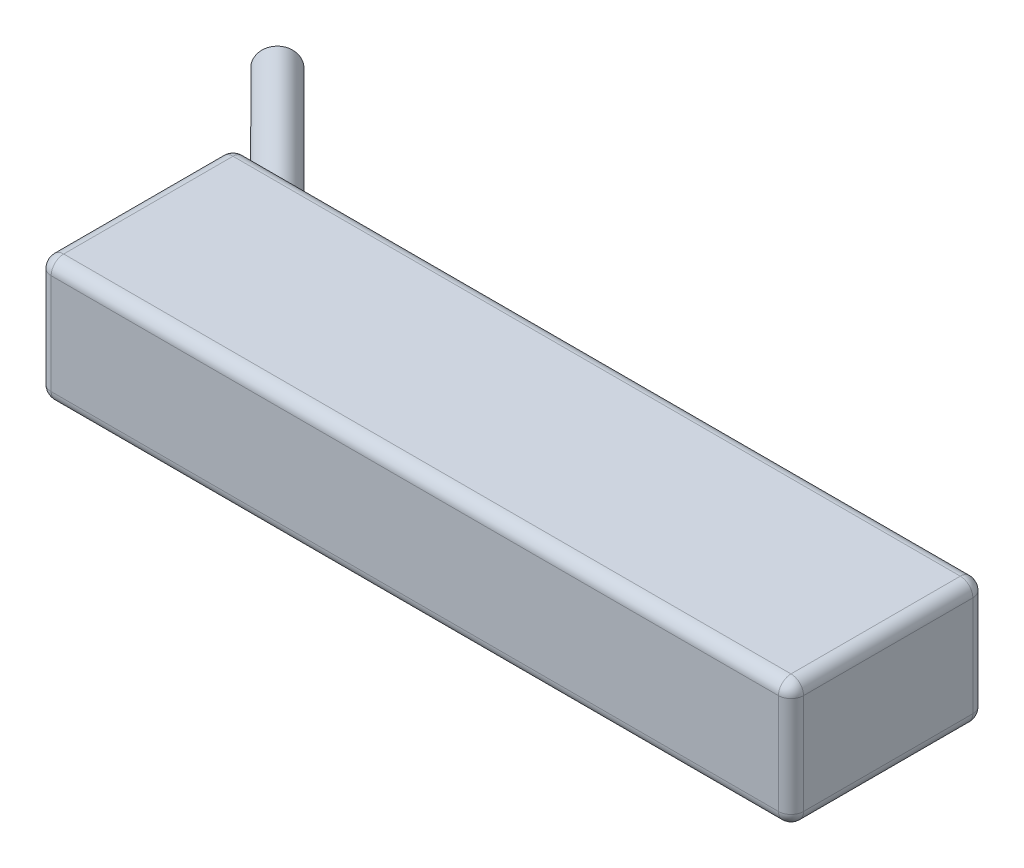
SolidWorks part; units mm, degrees
ref_plane "Front Plane" through (0, 0, 0) normal (0, 0, 1) x (1, 0, 0)
ref_plane "Top Plane" through (0, 0, 0) normal (0, 1, 0) x (1, 0, 0)
ref_plane "Right Plane" through (0, 0, 0) normal (1, 0, 0) x (0, 0, -1)
ref_axis "X" through (-88.99, 0, 0) along (1, 0, 0)
ref_axis "Y" through (0, 55, 0) along (0, -1, 0)
ref_axis "Z" through (0, 0, -88.99) along (0, 0, 1)
sketch "Sketch1" plane through (0, 0, 0) normal (0, 1, 0) x (1, 0, 0)
  line L1 (-60, 15.5) -> (60, 15.5)
  line L2 (-60, 15.5) -> (-60, -15.5)
  line L3 (-60, -15.5) -> (60, -15.5)
  line L4 (60, 15.5) -> (60, -15.5)
  line L5 (-60, 15.5) -> (60, -15.5) construction
  line L6 (-60, -15.5) -> (60, 15.5) construction
  point P0 (0, 0)
  dimension "D1" = 31
  dimension "D2" = 120
extrude "Boss-Extrude1" add sketch "Sketch1" along normal mid plane 20
sketch "Sketch3" plane through (0, 0, 0) normal (0, 1, 0) x (1, 0, 0)
  line L0 (-60, 15.5) -> (-60, 5.5)
  line L1 (-60, 5.5) -> (-50, 15.5)
  line L2 (-50, 15.5) -> (-60, 15.5)
  line L3 (-60, 15.5) -> (-55, 10.5) construction
  dimension "D1" = 45
  dimension "D2" = 10
ref_plane "Plane1" through (-32.75, 0, -32.75) normal (0.7071, 0, 0.7071) x (0.7071, 0, -0.7071)
sketch "Sketch4" plane through (-32.75, 0, -32.75) normal (0.7071, 0, 0.7071) x (0.7071, 0, -0.7071)
  line L0 (-26.4663, 4) -> (-26.4663, -4) construction
  line L1 (0, 0) -> (-26.4663, 0) construction
  line L2 (-31.4663, 10) -> (-31.4663, -10) construction
  circle A0 centre (-26.4663, 4) radius 3
  circle A1 centre (-26.4663, -4) radius 3
  dimension "D1" = 6
  dimension "D2" = 6
  dimension "D3" = 8
  dimension "D4" = 5
extrude "Boss-Extrude2" add sketch "Sketch4" against normal blind 30
fillet "Fillet1" radius 2 12 edges at (60, 0, -15.5) (-60, 0, -15.5) (-60, 0, 15.5) (60, 0, 15.5) (0, -10, -15.5) (-60, -10, 0) (0, -10, 15.5) (60, -10, 0) (0, 10, 15.5) (-60, 10, 0) (0, 10, -15.5) (60, 10, 0)
